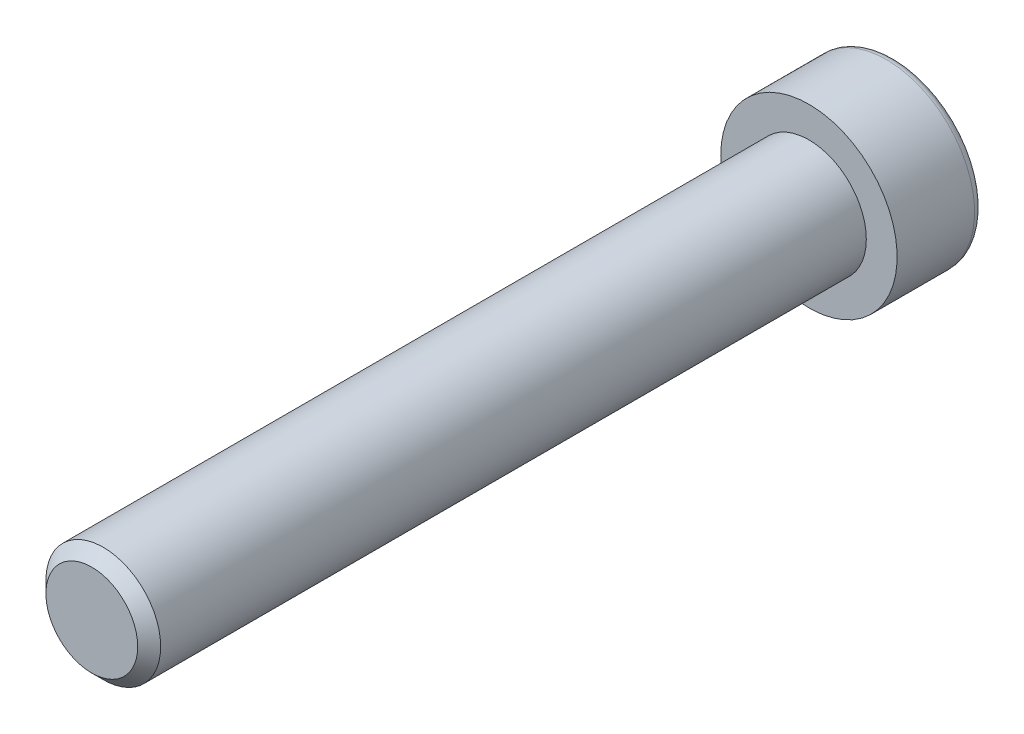
SolidWorks part; units mm, degrees
ref_plane "Plan1" through (0, 0, 0) normal (0, 0, 1) x (1, 0, 0)
ref_plane "Plan2" through (0, 0, 0) normal (0, 1, 0) x (1, 0, 0)
ref_plane "Plan3" through (0, 0, 0) normal (1, 0, 0) x (0, 0, -1)
ref_axis "Z Axis" through (0, 0, -50) along (0, 0, 1)
sketch "Esquisse1" plane through (0, 0, 0) normal (0, 1, 0) x (1, 0, 0)
  line L0 (0, 0) -> (0, 6) construction
  line L1 (0, 0) -> (6.15, 0)
  line L2 (0, 0) -> (0, 6)
  line L3 (0, 6) -> (5.55, 6)
  line L5 (6.15, 0) -> (6.15, 5.4)
  arc A0 (5.55, 6) -> (6.15, 5.4) centre (5.55, 5.4) cw
  dimension "D3" = 0.6
  dimension "D1" = 6.15
  dimension "D2" = 6
revolve "Base-Révolution" add sketch "Esquisse1" angle 360 about L0 reverse direction yes
sketch "Esquisse2" plane through (0, 0, -6) normal (0, 0, 1) x (1, 0, 0)
  line L0 (3, -1.7321) -> (3, 1.7321)
  line L1 (0, 0) -> (3, 1.7321) construction
  line L2 (1, 0) -> (3, 0) construction
  line L3 (0, 3.4641) -> (3, 1.7321)
  line L4 (0, -3.4641) -> (3, -1.7321)
  line L5 (0, 0) -> (0, 3) construction
  line L6 (-3, -1.7321) -> (-3, 1.7321)
  line L7 (0, 3.4641) -> (-3, 1.7321)
  line L8 (0, -3.4641) -> (-3, -1.7321)
  circle A0 centre (0, 0) radius 3 construction
  dimension "D2" = 30
  dimension "D1" = 6
extrude "enlev-mat-Extru1" cut sketch "Esquisse2" along normal blind 3
sketch "Esquisse3" plane through (0, 0, 0) normal (0, 1, 0) x (1, 0, 0)
  line L1 (0, 0) -> (0, -50) construction
  line L2 (0, 0) -> (4, 0)
  line L3 (0, 0) -> (0, -50)
  line L4 (0, -50) -> (4, -50)
  line L6 (4, 0) -> (4, -50)
  dimension "D1" = 50
  dimension "D2" = 4
revolve "Boss.-Révol.1" add sketch "Esquisse3" angle 360 about L1 reverse direction yes
sketch "Esquisse4" plane through (0, 0, 0) normal (0, 1, 0) x (1, 0, 0)
  line L0 (3.39, -50.061) -> (3.39, -49.939)
  line L1 (-4, -50) -> (4, -50) construction
  line L2 (3.39, -49.939) -> (4.061, -49.5516)
  line L3 (3.39, -50.061) -> (4.061, -50.4484)
  line L4 (4.061, -49.5516) -> (4.061, -50.4484)
  line L5 (4, -50) -> (4, 0) construction
  point P4 (4, -50)
  dimension "D2" = 0.061
  dimension "D3" = 0.061
  dimension "D4" = 0.671
  dimension "D5" = 60
  dimension "D1" = 0.61
  dimension "D6" = 60
chamfer "Chanfrein1" distance 0.8 angle 45 1 edges at (4, 0, 50)
sketch "Esquisse5" plane through (0, 0, 50) normal (0, 0, 1) x (1, 0, 0)
  circle A0 centre (0, 0) radius 4 construction
  circle A1 centre (0, 0) radius 4
curve "Hélice1" pitch 1 height 24 turns 24
sweep "Enlèvement de matière-Balayage1" [suppressed] cut profiles "Esquisse4" path "Hélice1"
equation "\"D3@Esquisse1\"=\"D2@Esquisse1\"/10"
equation "\"D1@Chanfrein1\"=\"D2@Esquisse3\"*0.2"
equation "\"D3@Esquisse4\"=0.1*\"D1@Esquisse4\""
equation "\"D4@Esquisse4\"=1.1*\"D1@Esquisse4\""
equation "\"D2@Esquisse4\"=0.1*\"D1@Esquisse4\""
equation "\"D1@Esquisse4\"=0.61*\"D4@Hélice1\""
